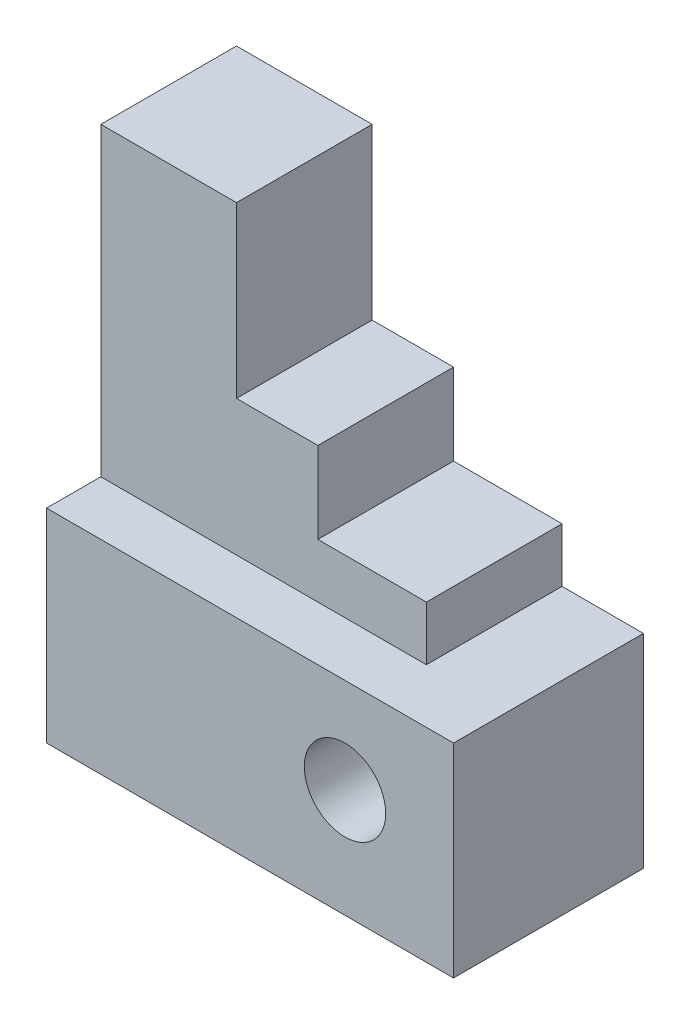
SolidWorks part; units mm, degrees
material "ABS"
ref_plane "Front Plane" through (0, 0, 0) normal (0, 0, 1) x (1, 0, 0)
ref_plane "Top Plane" through (0, 0, 0) normal (0, 1, 0) x (1, 0, 0)
ref_plane "Right Plane" through (0, 0, 0) normal (1, 0, 0) x (0, 0, -1)
sketch "Sketch2" plane through (0, 0, 0) normal (0, 0, 1) x (1, 0, 0)
  line L0 (0, 0) -> (60, 0)
  line L1 (60, 0) -> (60, 30)
  line L2 (60, 30) -> (48, 30)
  line L3 (48, 30) -> (48, 38)
  line L4 (48, 38) -> (32, 38)
  line L5 (32, 38) -> (32, 50)
  line L6 (32, 50) -> (20, 50)
  line L7 (20, 50) -> (20, 75)
  line L8 (20, 75) -> (0, 75)
  line L9 (0, 75) -> (0, 0)
  line L10 (48, 30) -> (0, 30)
  line L11 (32, 38) -> (0, 38)
  line L12 (20, 50) -> (0, 50)
  circle A0 centre (44, 16) radius 6
  dimension "D11" = 12
  dimension "D1" = 75
  dimension "D2" = 30
  dimension "D3" = 20
  dimension "D4" = 12
  dimension "D5" = 16
  dimension "D6" = 16
  dimension "D7" = 20
  dimension "D8" = 12
  dimension "D9" = 12
  dimension "D10" = 60
extrude "Boss-Extrude3" add sketch "Sketch2" along normal blind 28 contours L2 L10 L9 L0 L1 A0 region at (29.0614, 14.933, 0)
extrude "Boss-Extrude4" add sketch "Sketch2<5>" along normal blind 20 contours L4 L11 L9 L10 L3 | L6 L12 L9 L11 L5 | L12 L7 L8 L9 region at (24, 34, 0) region at (16, 44, 0) region at (10, 62.5, 0)
sketch "Sketch2<5>" plane through (0, 0, 0) normal (0, 0, 1) x (1, 0, 0) same geometry as "Sketch2"
